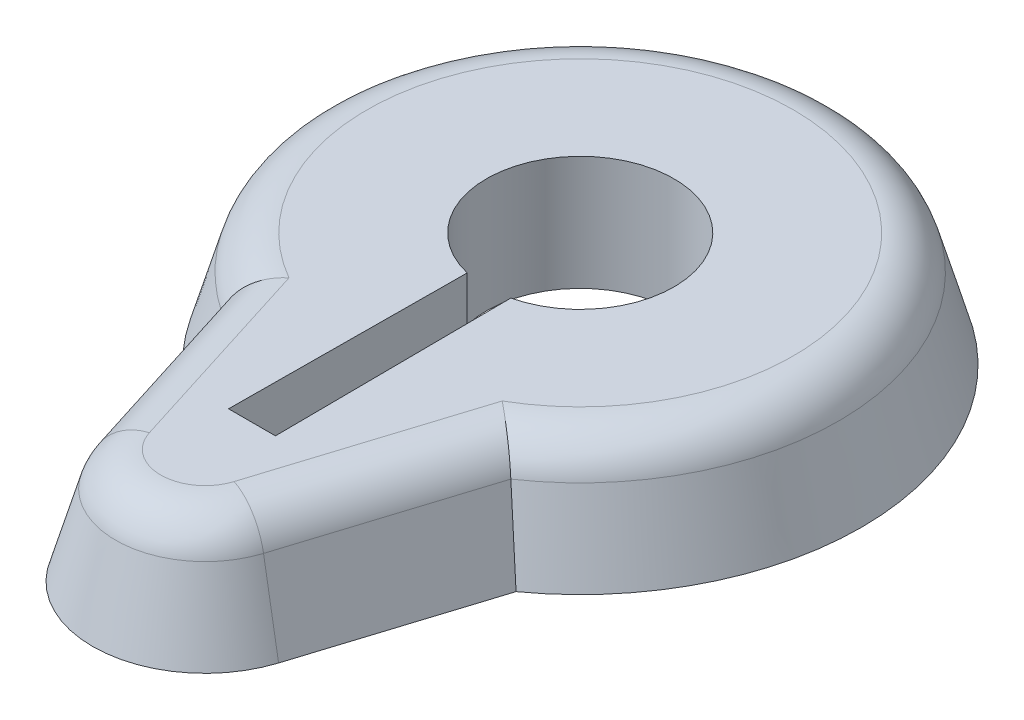
SolidWorks part; units mm, degrees
ref_plane "Front Plane" through (0, 0, 0) normal (0, 0, 1) x (1, 0, 0)
ref_plane "Top Plane" through (0, 0, 0) normal (0, 1, 0) x (1, 0, 0)
ref_plane "Right Plane" through (0, 0, 0) normal (1, 0, 0) x (0, 0, -1)
sketch "Sketch1" plane through (0, 0, 0) normal (0, 1, 0) x (1, 0, 0)
  line L0 (0, 0) -> (0, -1.3884) construction
  line L1 (-0.8757, 0.7822) -> (-0.5722, -0.1804)
  line L2 (0.8757, 0.7822) -> (0.5722, -0.1804)
  arc A1 (0.5722, -0.1804) -> (-0.5722, -0.1804) centre (0, 0) cw
  arc A2 (0.8757, 0.7822) -> (-0.8757, 0.7822) centre (0, 2) ccw
  point P2 (0.9404, -0.1647)
  dimension "D1" = 1.5
  dimension "D2" = 0.6
  dimension "D3" = 35
  dimension "D4" = 2
extrude "Boss-Extrude1" add sketch "Sketch1" along normal blind 0.61 draft 16
fillet "Fillet6" radius 0.25 4 edges at (0.5662, 0.61, -0.3822) (0, 0.61, 0.4251) (-0.5662, 0.61, -0.3822) (0, 0.61, -3.3251)
sketch "Sketch2" plane through (0, 0.61, 0) normal (0, 1, 0) x (1, 0, 0)
  line L1 (0.1162, 1.5137) -> (0.125, 0.25)
  line L4 (-0.125, 0.25) -> (0.125, 0.25)
  line L8 (-0.1162, 1.5137) -> (-0.125, 0.25)
  arc A0 (0.1162, 1.5137) -> (-0.1162, 1.5137) centre (0, 2) ccw
  point P6 (0, 1.5)
  dimension "D1" = 1
  dimension "D2" = 0.25
  dimension "D3" = 0.25
extrude "Cut-Extrude1" cut sketch "Sketch2" against normal through all
